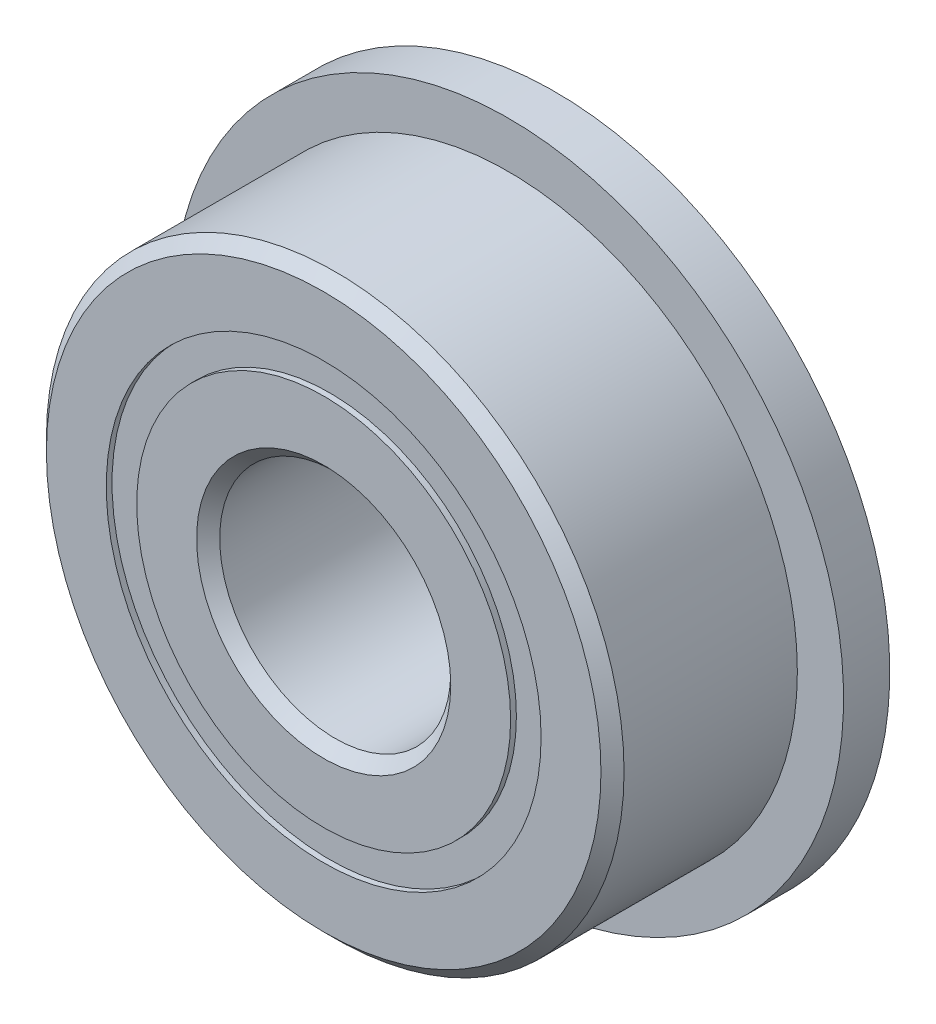
SolidWorks part; units mm, degrees
ref_plane "Front Plane" through (0, 0, 0) normal (0, 0, 1) x (1, 0, 0)
ref_plane "Top Plane" through (0, 0, 0) normal (0, 1, 0) x (1, 0, 0)
ref_plane "Right Plane" through (0, 0, 0) normal (1, 0, 0) x (0, 0, -1)
sketch "Sketch1" plane through (0, 0, 0) normal (1, 0, 0) x (0, 0, -1)
  line L0 (-2, 0) -> (2, 0) construction
  line L1 (0, 5) -> (0, -5) construction
  line L2 (1.8, 5) -> (-1.8, 5)
  line L3 (-1.8, 5) -> (-2, 4.8)
  line L4 (-2, 4.8) -> (-2, 3.7637)
  line L5 (-2, 3.7637) -> (-0.8889, 3.7637)
  line L6 (2, 3.7637) -> (0.8889, 3.7637)
  line L7 (2, 4.8) -> (2, 3.7637)
  line L8 (1.8, 5) -> (2, 4.8)
  line L9 (0, 5) -> (0, 3.5) construction
  line L10 (0, 3.5) -> (0, 2) construction
  arc A0 (-0.8889, 3.7637) -> (0.8889, 3.7637) centre (0, 3.5) cw
  point P14 (0, 2)
  dimension "Width" = 4
  dimension "OD" = 10
  dimension "D1" = 45
  dimension "D2" = 0.2
  dimension "Shaft Dia" = 4
  dimension "D3" = 1.7778
  dimension "D4" = 0.2637
revolve "Revolve1" add sketch "Sketch1" angle 360 about L0
sketch "Sketch3" plane through (0, 0, 0) normal (1, 0, 0) x (0, 0, -1)
  line L0 (-2, 3.2363) -> (-0.8889, 3.2363)
  line L1 (0, 5) -> (0, -5) construction
  line L2 (-2, 4.8) -> (-2, 3.7637) construction
  line L3 (-2, 3.2363) -> (-2, 2.2)
  line L4 (-1.8, 5) -> (-2, 4.8) construction
  line L5 (-2, 2.2) -> (-1.8, 2)
  line L6 (-1.8, 2) -> (1.8, 2)
  line L7 (1.8, 5) -> (1.8, -5) construction
  line L8 (1.8, 2) -> (2, 2.2)
  line L9 (2, -4.8) -> (2, 4.8) construction
  line L10 (2, 2.2) -> (2, 3.2363)
  line L11 (2, 3.2363) -> (0.8889, 3.2363)
  line L13 (1.8, 5) -> (2, 4.8) construction
  arc A0 (0.8889, 3.7637) -> (-0.8889, 3.7637) centre (0, 3.5) ccw construction
  arc A1 (0.8889, 3.2363) -> (-0.8889, 3.2363) centre (0, 3.5) cw
revolve "Revolve3" add sketch "Sketch3" angle 360 about L0
sketch "Sketch4" plane through (0, 0, 0) normal (1, 0, 0) x (0, 0, -1)
  line L0 (-0.9272, 3.5) -> (0.9272, 3.5)
  arc A2 (-0.9272, 3.5) -> (0.9272, 3.5) centre (0, 3.5) cw
  arc A3 (0.8889, 3.7637) -> (-0.8889, 3.7637) centre (0, 3.5) ccw construction
revolve "Revolve4" add sketch "Sketch4" angle 360 about L0
ref_axis "Axis1" through (0, 0, -2) along (0, 0, 1)
pattern_circular "CirPattern1" count 12 every 30 about axis through (0, 0, -2) along (0, 0, 1) of bodies 104
sketch "Sketch5" plane through (0, 0, 0) normal (1, 0, 0) x (0, 0, -1)
  line L0 (-2, 3.7637) -> (-0.8889, 3.7637) construction
  line L1 (-1.9, 3.7637) -> (-0.9272, 3.7637)
  line L2 (-1.9, 3.7637) -> (-1.9, 3.2363)
  line L3 (-1.9, 3.2363) -> (-0.9272, 3.2363)
  line L4 (-0.9272, 3.7637) -> (-0.9272, 3.2363)
  line L5 (-2, 3.2363) -> (-0.8889, 3.2363) construction
  line L6 (2, 3.7637) -> (0.8889, 3.7637) construction
  line L7 (1.9, 3.7637) -> (0.9272, 3.7637)
  line L8 (1.9, 3.7637) -> (1.9, 3.2363)
  line L9 (1.9, 3.2363) -> (0.9272, 3.2363)
  line L10 (0.9272, 3.7637) -> (0.9272, 3.2363)
  line L11 (2, 3.2363) -> (0.8889, 3.2363) construction
  line L12 (-1.8, 5) -> (-2, 4.8) construction
  point P18 (-1.9, 4.9)
revolve "Revolve5" add sketch "Sketch5" angle 360 about L0
sketch "Sketch6" plane through (0, 0, 0) normal (1, 0, 0) x (0, 0, -1)
  line L0 (2, 0) -> (-2, 0) construction
  line L1 (2, 3.7637) -> (1.2, 3.7637)
  line L2 (2, 3.7637) -> (2, 5.8)
  line L3 (2, 5.8) -> (1.2, 5.8)
  line L4 (1.2, 3.7637) -> (1.2, 5.8)
  dimension "Th" = 0.8
  dimension "Flange OD" = 11.6
revolve "Revolve6" add sketch "Sketch6" angle 360 about L0
equation "\"D2@Sketch1\" = \"Width@Sketch1\"*.05"
equation "\"D3@Sketch1\" = \"Width@Sketch1\"/2.25"
equation "\"D4@Sketch1\" = (((\"OD@Sketch1\"-\"Width@Sketch1\")/2)/3.25)/3.5"
equation "\"D2@CirPattern1\" = 360/\"Balls@CirPattern1\""
